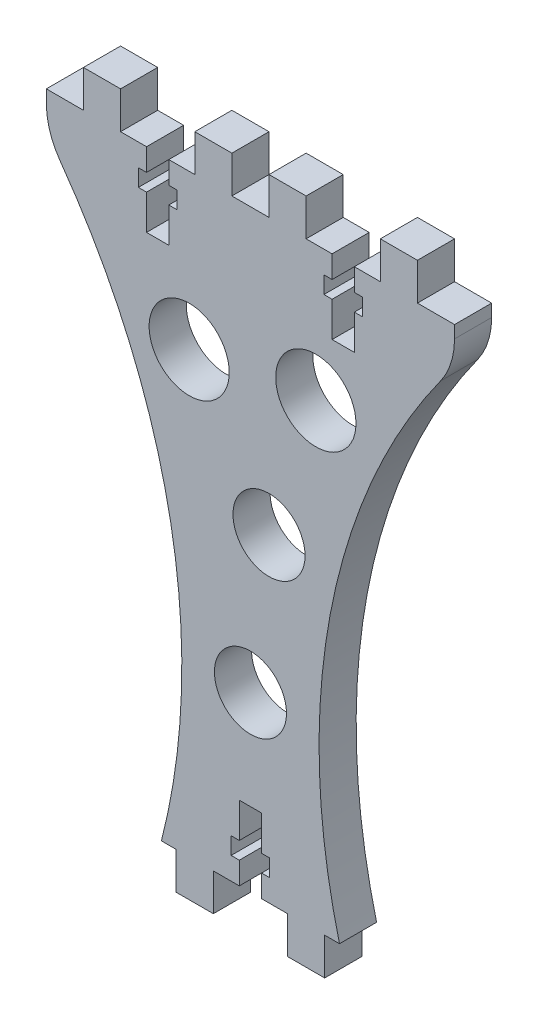
SolidWorks part; units mm, degrees
ref_plane "Plan de face" through (0, 0, 0) normal (0, 0, 1) x (1, 0, 0)
ref_plane "Plan de dessus" through (0, 0, 0) normal (0, 1, 0) x (1, 0, 0)
ref_plane "Plan de droite" through (0, 0, 0) normal (1, 0, 0) x (0, 0, -1)
sketch "Esquisse1" plane through (0, 0, 0) normal (0, 0, 1) x (1, 0, 0)
  line L0 (12, 0) -> (27.5, 75) construction
  line L1 (0, 0) -> (0, -30.9586) construction
  line L2 (-10, 0) -> (-12, 0)
  line L3 (-27.5, 75) -> (-27.5, 80)
  line L4 (-12, 0) -> (-27.5, 75) construction
  line L5 (-2.5, 80) -> (2.5, 80)
  line L6 (10, 0) -> (12, 0)
  line L8 (27.5, 75) -> (27.5, 80)
  line L9 (27.5, 80) -> (22.5, 80)
  line L10 (-22.5, 80) -> (-27.5, 80)
  circle A1 centre (8.8088, 61.7942) radius 5.4066
  circle A5 centre (-8.2559, 59.2161) radius 5.3954
  circle A6 centre (2.5, 42.9392) radius 4.8547
  circle A7 centre (0, 23.2964) radius 4.8548
  arc A8 (-27.5, 75) -> (-12, 0) centre (-96.138, 21.7131) cw
  arc A9 (27.5, 75) -> (12, 0) centre (96.138, 21.7131) ccw
  point P1 (-6.8031, 57.6712)
  point P16 (2.5, 42.9392)
  point P19 (0, 23.2964)
  point P20 (10, 59.6151)
  point P23 (8.8088, 61.7942)
  point P24 (-8.2559, 59.2161)
  point P31 (10, 0)
  line B0 (-2.6, 3) -> (-2.6, 5.3)
  line B1 (1.5, 5.3) -> (1.5, 10)
  line B2 (-1.5, 10) -> (-1.5, 5.3)
  line B3 (-2.6, 5.3) -> (-1.5, 5.3)
  line B4 (0, 0) -> (0, 11.2208) construction
  line B5 (-1.5, 0) -> (-5, 0)
  line B6 (-5, -5) -> (-10, -5)
  line B7 (-10, -5) -> (-10, 0)
  line B8 (-5, -5) -> (-5, 0)
  line B9 (1.5, 0) -> (5, 0)
  line B10 (5, 0) -> (5, -5)
  line B11 (5, -5) -> (10, -5)
  line B12 (10, -5) -> (10, 0)
  line B13 (-1.5, 0) -> (1.5, 0) construction
  line B14 (1.5, 0) -> (1.5, 3)
  line B15 (1.5, 5.3) -> (2.6, 5.3)
  line B16 (2.6, 3) -> (1.5, 3)
  line B17 (1.5, 10) -> (-1.5, 10)
  line B18 (-1.5, 3) -> (-2.6, 3)
  line B19 (2.6, 5.3) -> (2.6, 3)
  line B20 (-1.5, 3) -> (-1.5, 0)
  line B21 (0, 10) -> (0, 0) construction
  line B22 (15.1, 77) -> (15.1, 74.7)
  line B23 (11, 74.7) -> (11, 70)
  line B24 (14, 70) -> (14, 74.7)
  line B25 (15.1, 74.7) -> (14, 74.7)
  line B26 (12.5, 80) -> (12.5, 68.7792) construction
  line B27 (14, 80) -> (17.5, 80)
  line B28 (17.5, 85) -> (22.5, 85)
  line B29 (22.5, 85) -> (22.5, 80)
  line B30 (17.5, 85) -> (17.5, 80)
  line B31 (11, 80) -> (7.5, 80)
  line B32 (7.5, 80) -> (7.5, 85)
  line B33 (7.5, 85) -> (2.5, 85)
  line B34 (2.5, 85) -> (2.5, 80)
  line B35 (14, 80) -> (11, 80) construction
  line B36 (11, 80) -> (11, 77)
  line B37 (11, 74.7) -> (9.9, 74.7)
  line B38 (9.9, 77) -> (11, 77)
  line B39 (11, 70) -> (14, 70)
  line B40 (14, 77) -> (15.1, 77)
  line B41 (9.9, 74.7) -> (9.9, 77)
  line B42 (14, 77) -> (14, 80)
  line B43 (12.5, 70) -> (12.5, 80) construction
  line B44 (-15.1, 77) -> (-15.1, 74.7)
  line B45 (-11, 74.7) -> (-11, 70)
  line B46 (-14, 70) -> (-14, 74.7)
  line B47 (-15.1, 74.7) -> (-14, 74.7)
  line B48 (-12.5, 80) -> (-12.5, 68.7792) construction
  line B49 (-14, 80) -> (-17.5, 80)
  line B50 (-17.5, 85) -> (-22.5, 85)
  line B51 (-22.5, 85) -> (-22.5, 80)
  line B52 (-17.5, 85) -> (-17.5, 80)
  line B53 (-11, 80) -> (-7.5, 80)
  line B54 (-7.5, 80) -> (-7.5, 85)
  line B55 (-7.5, 85) -> (-2.5, 85)
  line B56 (-2.5, 85) -> (-2.5, 80)
  line B57 (-14, 80) -> (-11, 80) construction
  line B58 (-11, 80) -> (-11, 77)
  line B59 (-11, 74.7) -> (-9.9, 74.7)
  line B60 (-9.9, 77) -> (-11, 77)
  line B61 (-11, 70) -> (-14, 70)
  line B62 (-14, 77) -> (-15.1, 77)
  line B63 (-9.9, 74.7) -> (-9.9, 77)
  line B64 (-14, 77) -> (-14, 80)
  line B65 (-12.5, 70) -> (-12.5, 80) construction
  dimension "D6" = 86.8945
  dimension "D1" = 5
  dimension "D2" = 0
  dimension "D3" = 5
  dimension "D4" = 80
  dimension "D5" = 2
  dimension "D7" = 5
sketch_block_instance "Insert M3 plots ep 5mm-1"
sketch_block "Insert M3 plots ep 5mm" parameters "D1"=10, "D2"=5, "D3"=5
sketch_block_instance "Decoupe Insert M3-4"
sketch_block "Decoupe Insert M3" parameters "D1"=5.2, "D2"=3, "D3"=2.3, "D4"=3, "D5"=10
sketch_block_instance "Insert M3 plots ep 5mm-3"
sketch_block_instance "Insert M3 plots ep 5mm-4"
extrude "Boss.-Extru.1" add sketch "Esquisse1" along normal blind 5 contours B42 B40 B22 B25 B24 B39 B23 B37 B41 B38 B36 B31 B32 B33 B34 L4 L2 B7 B6 B8 B5 B20 B18 B0 B3 B2 B17 B1 B15 B19 B16 B14 B9 B10 B11 B12 L6 L0 L8 L9 B29 B28 B30 B27 region at (-0.1176, 48.4704, 0)
fillet "Congé1" radius 10 2 edges at (-27.5, 75, 2.5) (27.5, 75, 2.5)
